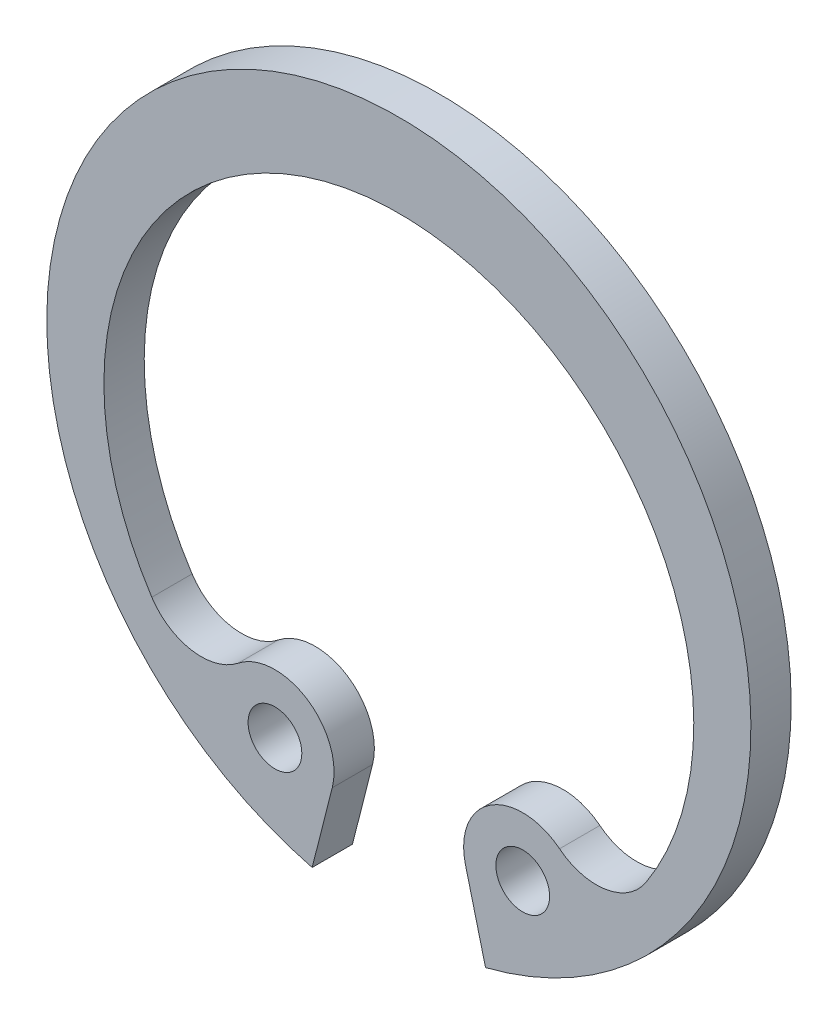
SolidWorks part; units mm, degrees
extrude "Body" add sketch "BodySke" against normal blind 1.5
sketch "BodySke" plane through (0, 0, 0) normal (0, 0, 1) x (1, 0, 0)
  line L0 (-1.5431, 0) -> (1.5431, 0) construction
  line L1 (0, 0) -> (0, 10) construction
  line L2 (3.2259, -12.6966) -> (2.4778, -9.7525)
  line L3 (-3.2259, -12.6966) -> (-2.4778, -9.7525)
  line L4 (0, 0) -> (10.3056, -8.0873) construction
  line L5 (0, 0) -> (-10.3056, -8.0873) construction
  line L6 (-4.3638, -8.2415) -> (-4.8563, -10.1799) construction
  line L7 (4.4253, -8.4832) -> (4.7949, -9.9382) construction
  arc A0 (-2.4778, -9.7525) -> (-5.9802, -7.4894) centre (-4.6101, -9.2107) ccw
  arc A1 (5.9802, -7.4894) -> (2.4778, -9.7525) centre (4.6101, -9.2107) ccw
  arc A2 (9.0862, -7.1304) -> (-9.0862, -7.1304) centre (0, -0.9749) ccw construction
  arc A3 (3.2259, -12.6966) -> (-3.2259, -12.6966) centre (0, 0) ccw
  circle A4 centre (4.6101, -9.2107) radius 1
  circle A5 centre (-4.6101, -9.2107) radius 1
  circle A6 centre (4.6101, -9.2107) radius 2.2 construction
  arc A7 (9.193, -6.9698) -> (-9.193, -6.9698) centre (0, -0.9749) ccw
  arc A8 (-4.6101, -9.2107) -> (4.6101, -9.2107) centre (0, 0) ccw construction
  arc A9 (-9.193, -6.9698) -> (-5.9802, -7.4894) centre (-7.3502, -5.7681) ccw
  arc A10 (5.9802, -7.4894) -> (9.193, -6.9698) centre (7.3502, -5.7681) ccw
  dimension "GrooveDia" = 26.2
  dimension "TipRad" = 2.2
  dimension "HoleDia" = 2
ref_plane "Plane1" through (0, 0, 0) normal (0, 0, 1) x (1, 0, 0)
ref_plane "Plane2" through (0, 0, 0) normal (0, 1, 0) x (1, 0, 0)
ref_plane "Plane3" through (0, 0, 0) normal (1, 0, 0) x (0, 0, -1)
sketch "Clipboard" plane through (0, 0, 0) normal (0, 0, 1) x (1, 0, 0)
  line L0 (0, 0) -> (3.1, 0)
  line L1 (0, 0) -> (0, 1.55)
  line L2 (0, 0) -> (0, -5)
  circle A0 centre (0, 0) radius 1
  circle A1 centre (0, 0) radius 12.5
  dimension "HoleDia" = 2
sketch "ModLugSke" plane through (0, 0, 0) normal (0, 0, 1) x (1, 0, 0)
  line L0 (3.2259, -12.6966) -> (2.0191, -7.9469)
  line L1 (-3.2259, -12.6966) -> (-2.0191, -7.9469)
  line L2 (7.0994, -3.8998) -> (11.4817, -6.3071) construction
  line L3 (-7.0994, -3.8998) -> (-11.4817, -6.3071) construction
  line L4 (-3.2259, -12.6966) -> (-2.4778, -9.7525) construction
  line L5 (2.4778, -9.7525) -> (3.2259, -12.6966) construction
  line L6 (0, 0) -> (0, -18.0732) construction
  line L7 (9.9888, -5.487) -> (11.4817, -6.3071)
  line L8 (-11.4817, -6.3071) -> (-9.9888, -5.487)
  arc A0 (3.2259, -12.6966) -> (11.4817, -6.3071) centre (0, 0) ccw
  arc A1 (-4.8943, -6.4541) -> (-2.0902, -7.8257) centre (0, 0) ccw
  arc A2 (3.2259, -12.6966) -> (-3.2259, -12.6966) centre (0, 0) ccw construction
  arc A3 (5.9802, -7.4894) -> (2.4778, -9.7525) centre (4.6101, -9.2107) ccw construction
  arc A4 (-4.8943, -6.4541) -> (-5.0179, -6.4562) centre (-4.9547, -6.5338) ccw
  arc A5 (-9.9888, -5.487) -> (-5.0179, -6.4562) centre (-7.0994, -3.8998) ccw
  arc A6 (9.193, -6.9698) -> (-9.193, -6.9698) centre (0, -0.9749) ccw construction
  arc A7 (5.0179, -6.4562) -> (9.9888, -5.487) centre (7.0994, -3.8998) ccw
  arc A8 (2.0902, -7.8257) -> (4.8943, -6.4541) centre (0, 0) ccw
  arc A9 (-11.4817, -6.3071) -> (-3.2259, -12.6966) centre (0, 0) ccw
  circle A10 centre (-4.6101, -9.2107) radius 1
  circle A11 centre (-4.6101, -9.2107) radius 1 construction
  circle A12 centre (4.6101, -9.2107) radius 1
  circle A13 centre (4.6101, -9.2107) radius 1 construction
  arc A14 (-2.0902, -7.8257) -> (-2.0191, -7.9469) centre (-2.116, -7.9223) cw
  arc A15 (2.0902, -7.8257) -> (2.0191, -7.9469) centre (2.116, -7.9223) ccw
  arc A16 (4.8943, -6.4541) -> (5.0179, -6.4562) centre (4.9547, -6.5338) cw
  point P43 (1.9946, -7.8506)
  dimension "D1" = 0.1
extrude "ModLug" [suppressed] add sketch "ModLugSke" against normal through all
sketch "UnlSke" [suppressed] plane through (0, 0, 0) normal (0, 0, 1) x (1, 0, 0)
  line L0 (1.9946, -7.8506) -> (3.2259, -12.6966)
  line L1 (-1.9946, -7.8506) -> (-3.2259, -12.6966)
  line L2 (-3.2259, -12.6966) -> (-2.0191, -7.9469) construction
  line L3 (2.0191, -7.9469) -> (3.2259, -12.6966) construction
  arc A0 (1.9946, -7.8506) -> (-1.9946, -7.8506) centre (0, 0) ccw
  arc A1 (3.2259, -12.6966) -> (-3.2259, -12.6966) centre (0, 0) ccw
  arc A2 (3.2259, -12.6966) -> (-3.2259, -12.6966) centre (0, 0) ccw construction
  circle A4 centre (-4.6101, -9.2107) radius 1
  circle A5 centre (4.6101, -9.2107) radius 1
  circle A6 centre (4.6101, -9.2107) radius 1 construction
  circle A7 centre (-4.6101, -9.2107) radius 1 construction
  arc A8 (2.0902, -7.8257) -> (4.8943, -6.4541) centre (0, 0) ccw construction
extrude "Unlug" [suppressed] add sketch "UnlSke" against normal through all
equation "' \"BoreDia@Clipboard\" = 20"
equation "' \"Thickness@Body\" = 1.5"
equation "' \"GrooveDia@BodySke\" = 21"
equation "' \"LugSection@Clipboard\" = 4.5"
equation "' \"LargeSection@Clipboard\" = 2.4"
equation "' \"HoleDia@Clipboard\" = 2"
equation "' \"BoreDia@Clipboard\" = 25"
equation "' \"GrooveDia@BodySke\" = 26.2"
equation "' \"LugSection@Clipboard\" = 5"
equation "' \"LargeSection@Clipboard\" = 3.1"
equation "\"SmallSection@Clipboard\" = \"LargeSection@Clipboard\" * 0.5"
equation "\"TipRad@BodySke\" = (\"LugSection@Clipboard\" - (\"GrooveDia@BodySke\" / 2  -  \"BoreDia@Clipboard\" / 2 ) ) / 2"
equation "\"HoleOffsetRad@BodySke\" = (\"GrooveDia@BodySke\" / 2) - \"LugSection@Clipboard\"  + \"TipRad@BodySke\""
equation "\"LargeRad@BodySke\" =  \"GrooveDia@BodySke\" / 2 -  \"LargeSection@Clipboard\""
equation "\"SmallRad@BodySke\" =  \"GrooveDia@BodySke\" / 2 -  \"SmallSection@Clipboard\""
equation "\"HoleDia@BodySke\" =  \"HoleDia@Clipboard\""
equation "\"FilletRad@BodySke\" = \"TipRad@BodySke\" * 1.0"
equation "\"GapAngle@BodySke\" = 360 - 0.965 * 360 * ( \"BoreDia@Clipboard\" /  \"GrooveDia@BodySke\")"
equation "\"LugAng@ModLugSke\" = \"GapAngle@BodySke\"  + 2 * 360 * (\"LugSection@Clipboard\" / (\"BoreDia@Clipboard\" * 3.1416))"
